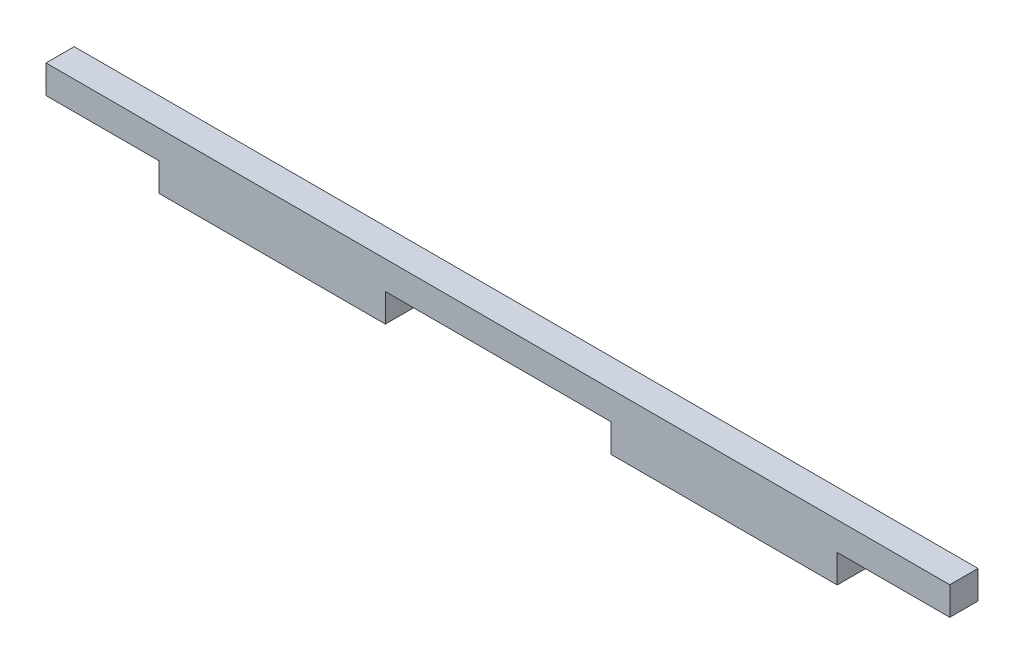
SolidWorks part; units mm, degrees
ref_plane "Front Plane" through (0, 0, 0) normal (0, 0, 1) x (1, 0, 0)
ref_plane "Top Plane" through (0, 0, 0) normal (0, 1, 0) x (1, 0, 0)
ref_plane "Right Plane" through (0, 0, 0) normal (1, 0, 0) x (0, 0, -1)
sketch "Sketch1" plane through (0, 0, 0) normal (0, 0, 1) x (1, 0, 0)
  line L0 (-12.6492, -1.5875) -> (12.7, -1.5875)
  line L1 (-50.8, 1.5875) -> (50.8, 1.5875)
  line L2 (-50.8, 1.5875) -> (-50.8, -1.5875)
  line L3 (-50.8, -1.5875) -> (-38.1, -1.5875)
  line L4 (50.8, 1.5875) -> (50.8, -1.5875)
  line L5 (-50.8, 1.5875) -> (50.8, -1.5875) construction
  line L6 (-50.8, -1.5875) -> (50.8, 1.5875) construction
  line L8 (-12.6492, -1.5875) -> (-12.6492, -4.7625)
  line L9 (-12.6492, -4.7625) -> (-38.1, -4.7625)
  line L10 (-38.1, -1.5875) -> (-38.1, -4.7625)
  line L12 (12.7, -1.5875) -> (12.7, -4.7625)
  line L13 (12.7, -4.7625) -> (38.1508, -4.7625)
  line L14 (38.1508, -1.5875) -> (38.1508, -4.7625)
  line L15 (38.1508, -1.5875) -> (50.8, -1.5875)
  point P0 (0, 0)
  point P14 (25.4254, -4.7625)
  point P15 (-25.3746, -4.7625)
  dimension "D1" = 3.175
  dimension "D2" = 101.6
  dimension "D3" = 3.175
  dimension "D4" = 25.4508
  dimension "D5" = 50.8
  dimension "D6" = 25.4508
  dimension "D7" = 12.7
extrude "Boss-Extrude1" add sketch "Sketch1" along normal mid plane 3.175
